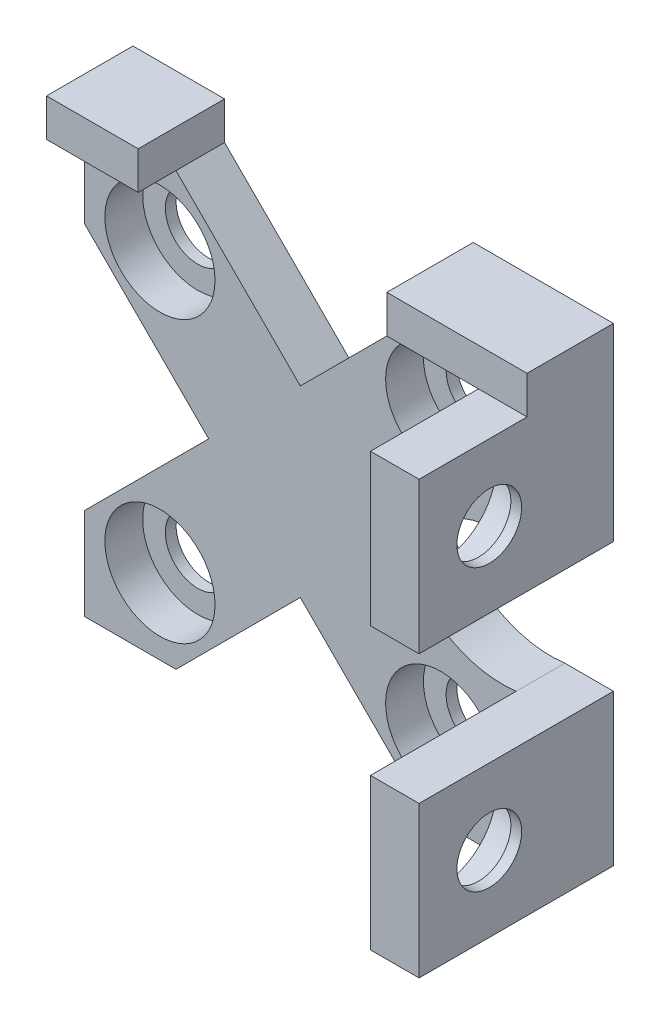
SolidWorks part; units mm, degrees
ref_plane "Plano frontal" through (0, 0, 0) normal (0, 0, 1) x (1, 0, 0)
ref_plane "Plano superior" through (0, 0, 0) normal (0, 1, 0) x (1, 0, 0)
ref_plane "Plano direito" through (0, 0, 0) normal (1, 0, 0) x (0, 0, -1)
sketch "Esboço1" plane through (0, 0, 0) normal (0, 0, 1) x (1, 0, 0)
  line L0 (-8.4853, 0) -> (-20, 11.5147)
  line L1 (-11.5147, 20) -> (-20, 20)
  line L2 (-11.5147, 20) -> (0, 8.4853)
  line L3 (0, 8.4853) -> (0, 0)
  line L4 (0, 0) -> (-8.4853, 0)
  line L5 (-20, 20) -> (-20, 11.5147)
  point P1 (7.079, 9.8915)
  point P3 (0, 0)
  dimension "D1" = 12
  dimension "D2" = 45
  dimension "D3" = 20
extrude "Ressalto-extrusão1" add sketch "Esboço1" along normal blind 4.5
sketch "Esboço2" plane through (0, 0, 4.5) normal (0, 0, 1) x (1, 0, 0)
  line L0 (-20, 20) -> (0, 0) construction
  line L1 (0, 0) -> (0, 8.4853) construction
  circle A0 centre (-13, 13) radius 5.1
  point P6 (-6.6212, 15.1064)
  point P7 (-5.3132, 13.7985)
  dimension "D1" = 10.2
  dimension "D2" = 13
extrude "Corte-extrusão1" cut sketch "Esboço2" against normal blind 3.5
sketch "Esboço3" plane through (0, 0, 1) normal (0, 0, 1) x (1, 0, 0)
  circle A0 centre (-13, 13) radius 3
  dimension "D1" = 6
extrude "Corte-extrusão2" cut sketch "Esboço3" against normal blind 3.5
mirror "Espelhar1" about plane through (0, 0, 0) normal (1, 0, 0) of "Corte-extrusão2", "Corte-extrusão1", "Ressalto-extrusão1"
mirror "Espelhar2" about plane through (0, 0, 0) normal (0, 1, 0) of "Corte-extrusão2", "Ressalto-extrusão1", "Corte-extrusão1", "Espelhar1"
sketch "Esboço5" plane through (20, 0, 0) normal (1, 0, 0) x (0, 0, -1)
  line L0 (-4.5, 20) -> (-4.5, 11.5147) construction
  line L1 (0, 20) -> (-18, 20)
  line L2 (0, 20) -> (0, 6)
  line L3 (0, 6) -> (-18, 6)
  line L4 (-18, 20) -> (-18, 6)
  circle A0 centre (-11.5, 13) radius 5 construction
  point P7 (-10.4977, 13)
  point P8 (0, 0)
  dimension "D2" = 10
  dimension "D1" = 13
  dimension "D3" = 18
  dimension "D4" = 7
  dimension "D5" = 14
extrude "Ressalto-extrusão2" add sketch "Esboço5" along normal blind 4.5
sketch "Esboço6" plane through (20, 0, 0) normal (-1, 0, 0) x (0, 0, 1)
  circle A1 centre (11.5, 13) radius 5.15
  dimension "D1" = 10.3
extrude "Corte-extrusão3" cut sketch "Esboço6" against normal blind 3.5
sketch "Esboço7" plane through (23.5, 0, 0) normal (-1, 0, 0) x (0, 0, 1)
  circle A0 centre (11.5, 13) radius 3
  dimension "D1" = 6
extrude "Corte-extrusão4" cut sketch "Esboço7" against normal blind 3.5
mirror "Espelhar3" about plane through (0, 0, 0) normal (0, 1, 0) of "Corte-extrusão4", "Ressalto-extrusão2", "Corte-extrusão3"
fillet "Filete1" radius 10 2 edges at (20, 11.5147, 2.25) (20, -11.5147, 2.25)
sketch "Esboço8" plane through (0, 20, 0) normal (0, 1, 0) x (1, 0, 0)
  line L0 (24.5, 0) -> (24.5, -18) construction
  line L1 (-20, 0) -> (-11.5147, 0)
  line L2 (-20, 0) -> (-20, -8)
  line L3 (-20, -8) -> (-11.5147, -8)
  line L4 (-11.5147, 0) -> (-11.5147, -8)
  line L5 (11.5147, 0) -> (24.5, 0)
  line L6 (11.5147, 0) -> (11.5147, -8)
  line L7 (11.5147, -8) -> (24.5, -8)
  line L8 (24.5, 0) -> (24.5, -8)
  point P12 (-11.5147, 0)
  dimension "D1" = 8
extrude "Ressalto-extrusão3" add sketch "Esboço8" along normal blind 3.5
